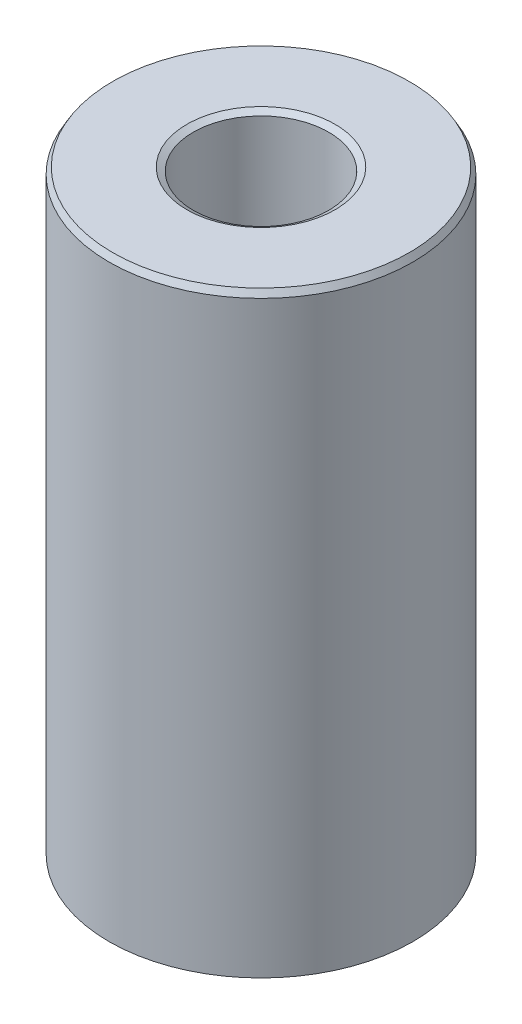
SolidWorks part; units mm, degrees
ref_plane "Front Plane" through (0, 0, 0) normal (0, 0, 1) x (1, 0, 0)
ref_plane "Top Plane" through (0, 0, 0) normal (0, 1, 0) x (1, 0, 0)
ref_plane "Right Plane" through (0, 0, 0) normal (1, 0, 0) x (0, 0, -1)
sketch "Sketch1" plane through (0, 0, 0) normal (0, 1, 0) x (1, 0, 0)
  circle A0 centre (0, 0) radius 5
  dimension "SLEEVE_OD" = 10
extrude "Boss-Extrude1" add sketch "Sketch1" along normal blind 19.6942
sketch "Sketch2" plane through (0, 0, 0) normal (0, 1, 0) x (1, 0, 0)
  circle A0 centre (0, 0) radius 2.2293
  dimension "BORE_D" = 4.4587
extrude "Cut-Extrude1" cut sketch "Sketch2" along normal through all
chamfer "Chamfer1" distance 0.2088 angle 30 4 edges at (0, 19.6942, 2.2293) (0, 0, 2.2293) (0, 0, 5) (0, 19.6942, 5) first distance on face at (0, 19.6942, 2.2293) first distance on face at (0, 0, 2.2293) first distance on face at (0, 19.6942, 5)
